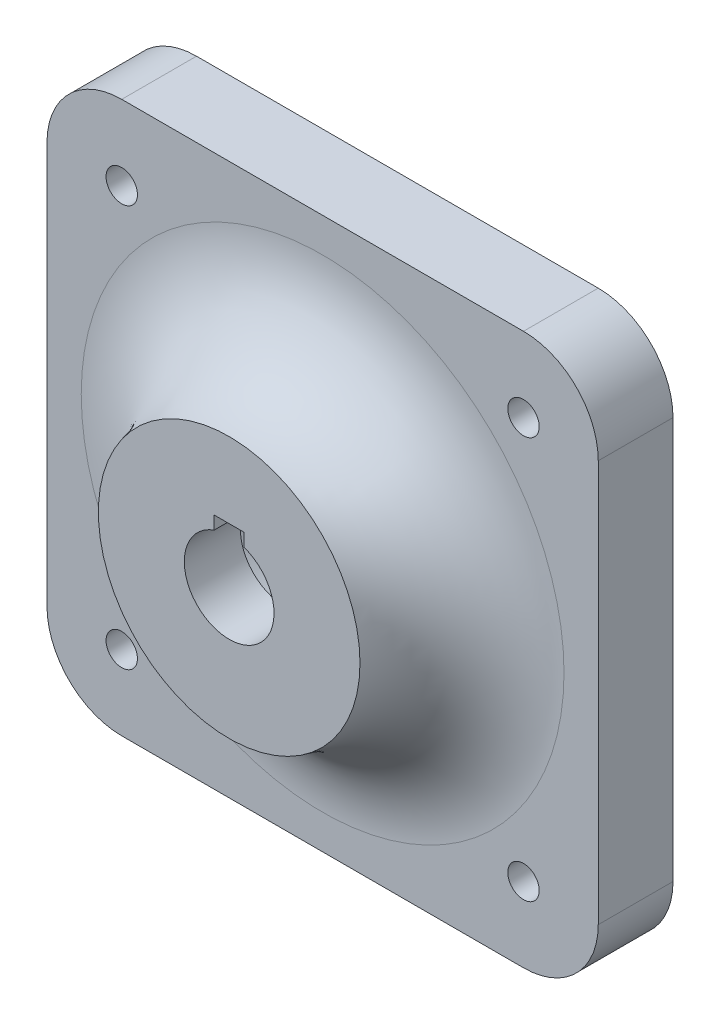
SolidWorks part; units mm, degrees
ref_plane "Front Plane" through (0, 0, 0) normal (0, 0, 1) x (1, 0, 0)
ref_plane "Top Plane" through (0, 0, 0) normal (0, 1, 0) x (1, 0, 0)
ref_plane "Right Plane" through (0, 0, 0) normal (1, 0, 0) x (0, 0, -1)
sketch "Spacing" plane through (0, 0, 0) normal (0, 0, 1) x (1, 0, 0)
  line L1 (-26.8701, -26.8701) -> (26.8701, -26.8701)
  line L2 (-26.8701, -26.8701) -> (-26.8701, 26.8701)
  line L3 (-26.8701, 26.8701) -> (26.8701, 26.8701)
  line L4 (26.8701, -26.8701) -> (26.8701, 26.8701)
  line L5 (-26.8701, -26.8701) -> (26.8701, 26.8701) construction
  line L6 (-26.8701, 26.8701) -> (26.8701, -26.8701) construction
  point P0 (0, 0)
  dimension "D1" = 76
sketch "Sketch1" plane through (0, 0, 7) normal (0, 0, 1) x (1, 0, 0)
  line L0 (36.8701, -26.8701) -> (36.8701, 26.8701)
  line L1 (26.8701, 36.8701) -> (-26.8701, 36.8701)
  line L2 (-36.8701, 26.8701) -> (-36.8701, -26.8701)
  line L3 (26.8701, -36.8701) -> (-26.8701, -36.8701)
  arc A0 (26.8701, -36.8701) -> (36.8701, -26.8701) centre (26.8701, -26.8701) ccw
  arc A1 (-36.8701, -26.8701) -> (-26.8701, -36.8701) centre (-26.8701, -26.8701) ccw
  arc A2 (-26.8701, 36.8701) -> (-36.8701, 26.8701) centre (-26.8701, 26.8701) ccw
  arc A3 (36.8701, 26.8701) -> (26.8701, 36.8701) centre (26.8701, 26.8701) ccw
  circle A6 centre (26.8701, -26.8701) radius 2.1
  circle A7 centre (-26.8701, -26.8701) radius 2.1
  circle A8 centre (-26.8701, 26.8701) radius 2.1
  circle A9 centre (26.8701, 26.8701) radius 2.1
  dimension "D1" = 20
  dimension "D2" = 4.2
extrude "Boss-Extrude1" add sketch "Sketch1" along normal blind 10 from offset 2
sketch "Sketch7" plane through (0, 0, 9) normal (0, 0, -1) x (-1, 0, 0)
  circle A0 centre (26.8701, -26.8701) radius 2.1 construction
  circle A1 centre (26.8701, -26.8701) radius 2.1
  circle A2 centre (26.8701, -26.8701) radius 3.6
  circle A3 centre (-26.8701, -26.8701) radius 3.6
  circle A4 centre (-26.8701, -26.8701) radius 2.1
  circle A5 centre (-26.8701, 26.8701) radius 3.6
  circle A6 centre (-26.8701, 26.8701) radius 2.1
  circle A7 centre (26.8701, 26.8701) radius 3.6
  circle A8 centre (26.8701, 26.8701) radius 2.1
  dimension "D1" = 7.2
  dimension "D2" = 2
  dimension "D3" = 2
extrude "Boss-Extrude3" add sketch "Sketch7" along normal up to surface (2 mm away)
sketch "Sketch3" plane through (0, 0, 19) normal (0, 0, 1) x (1, 0, 0)
  circle A0 centre (0, 0) radius 17.5
  dimension "D1" = 35
extrude "Boss-Extrude2" add sketch "Sketch3" along normal blind 12.5
sketch "Sketch2" plane through (0, 0, 9) normal (0, 0, -1) x (-1, 0, 0)
  circle A0 centre (0, 0) radius 15
  dimension "D1" = 30
extrude "Cut-Extrude1" cut sketch "Sketch2" against normal blind 15
fillet "Fillet1" radius 15 1 edges at (17.5, 0, 19)
sketch "Sketch4" plane through (0, 0, 31.5) normal (0, 0, 1) x (1, 0, 0)
  circle A0 centre (0, 0) radius 6
  dimension "D1" = 12
extrude "Cut-Extrude2" cut sketch "Sketch4" against normal through all
sketch "Sketch5" plane through (0, 0, 31.5) normal (0, 0, 1) x (1, 0, 0)
  line L1 (2, 7.4) -> (-2, 7.4)
  line L2 (2, 7.4) -> (2, 5.6569)
  line L3 (2, 5.6569) -> (-2, 5.6569)
  line L4 (-2, 7.4) -> (-2, 5.6569)
  line L5 (2, 7.4) -> (-2, 5.6569) construction
  line L6 (2, 5.6569) -> (-2, 7.4) construction
  circle A0 centre (0, 0) radius 6 construction
  point P0 (0, 6.5284)
  dimension "D1" = 4
  dimension "D2" = 1.4
extrude "Cut-Extrude3" cut sketch "Sketch5" against normal through all
